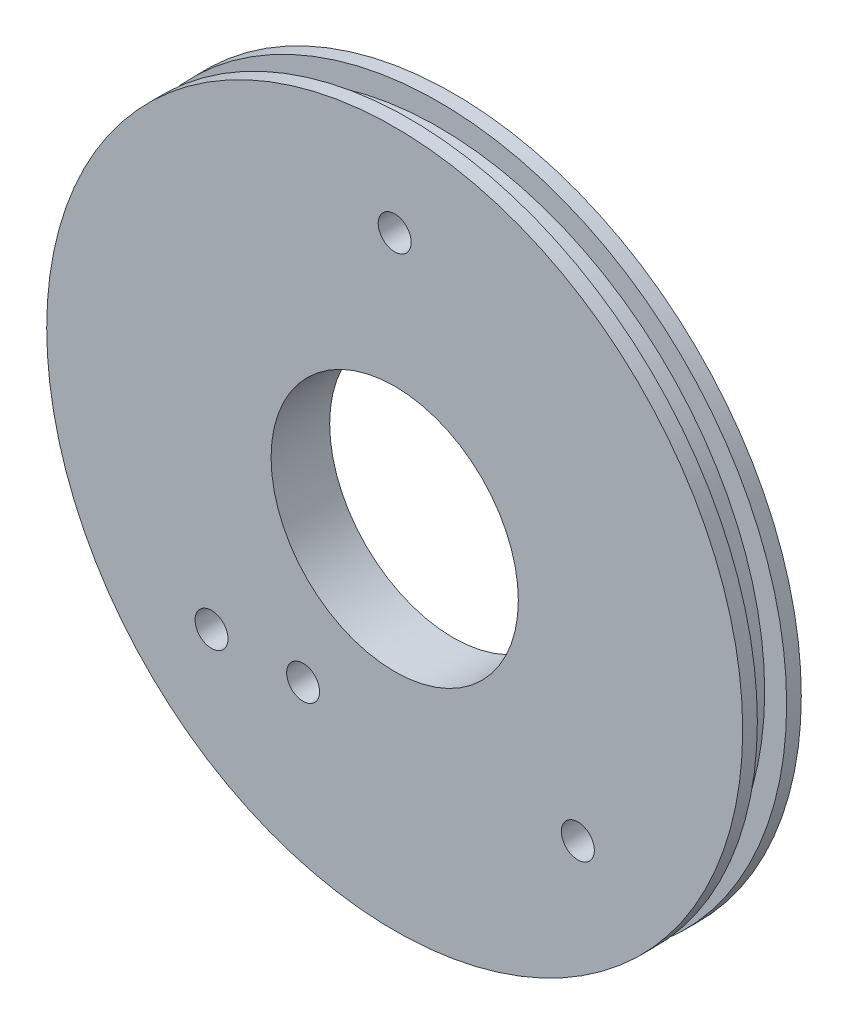
SolidWorks part; units mm, degrees
ref_plane "Front Plane" through (0, 0, 0) normal (0, 0, 1) x (1, 0, 0)
ref_plane "Top Plane" through (0, 0, 0) normal (0, 1, 0) x (1, 0, 0)
ref_plane "Right Plane" through (0, 0, 0) normal (1, 0, 0) x (0, 0, -1)
sketch "Sketch2" plane through (0, 0, 0) normal (0, 0, 1) x (1, 0, 0)
  circle A0 centre (0, 0) radius 89
  circle A1 centre (0, 0) radius 95
  dimension "180" = 178
  dimension "D2" = 190
extrude "Boss-Extrude1" add sketch "Sketch2" along normal blind 8 and the other way blind 8 contours A1 A0 | A0 region at (-92.313, 0, 0)
extrude "Cut-Extrude1" cut sketch "Sketch2<5>" against normal blind 4 and the other way blind 4
sketch "Sketch2<5>" plane through (0, 0, 0) normal (0, 0, 1) x (1, 0, 0) same geometry as "Sketch2"
sketch "Sketch3" plane through (0, 0, 8) normal (0, 0, 1) x (1, 0, 0)
  line L0 (0, 33.75) -> (0, -33.75) construction
  line L1 (41.5, 33.75) -> (-78.5, 33.75)
  line L2 (41.5, 33.75) -> (41.5, -33.75)
  line L3 (41.5, -33.75) -> (-78.5, -33.75) construction
  line L4 (-78.5, 33.75) -> (-78.5, -33.75) construction
  line L5 (31, 33.75) -> (31, -33.75) construction
  line L6 (41.5, 0) -> (-78.5, 0) construction
  line L7 (-78.5, 28.75) -> (-43.5, 28.75)
  line L8 (-43.5, 28.75) -> (-43.5, -33.75)
  line L9 (-78.5, 33.75) -> (-78.5, 28.75)
  line L10 (-43.5, -33.75) -> (41.5, -33.75)
  circle A0 centre (0, 0) radius 31
  circle A1 centre (0, 0) radius 33.75
  point P9 (0, 0)
  dimension "D3" = 62
  dimension "D7" = 67.5
  dimension "D1" = 10.5
  dimension "D2" = 120
  dimension "D4" = 67.5
  dimension "D5" = 5
  dimension "D6" = 35
sketch "Sketch4" plane through (0, 0, -8) normal (0, 0, 1) x (1, 0, 0)
  line L0 (0, 33.75) -> (0, -33.75) construction
  line L1 (41.5, 33.75) -> (-78.5, 33.75)
  line L2 (41.5, 33.75) -> (41.5, -33.75)
  line L3 (41.5, -33.75) -> (-78.5, -33.75) construction
  line L4 (-78.5, 33.75) -> (-78.5, -33.75) construction
  line L5 (31, 33.75) -> (31, -33.75) construction
  line L6 (41.5, 0) -> (-78.5, 0) construction
  line L7 (-78.5, 28.75) -> (-43.5, 28.75)
  line L8 (-43.5, 28.75) -> (-43.5, -33.75)
  line L9 (-78.5, 33.75) -> (-78.5, 28.75)
  line L10 (-43.5, -33.75) -> (41.5, -33.75)
  circle A0 centre (0, 0) radius 31
  point P9 (0, 0)
  dimension "D3" = 62
  dimension "D1" = 10.5
  dimension "D2" = 120
  dimension "D4" = 67.5
  dimension "D5" = 5
  dimension "D6" = 35
ref_plane "Plane1" through (0, -33.75, 0) normal (0, 1, 0) x (1, 0, 0)
sketch "Sketch7" plane through (0, 0, 8) normal (0, 0, 1) x (1, 0, 0)
  line L0 (0, -33.75) -> (0, -48.75) construction
  line L1 (-50, -48.75) -> (50, -48.75) construction
  line L2 (0, -48.75) -> (20, -48.75) construction
  line L3 (0, -48.75) -> (-6.4741, -48.75) construction
  circle A0 centre (-50, -48.75) radius 4.5
  circle A1 centre (50, -48.75) radius 4.5
  circle A5 centre (-25, -48.75) radius 4.5
  point P7 (0, -48.75)
  dimension "D3" = 9
  dimension "D4" = 9
  dimension "D5" = 9
  dimension "D1" = 100
  dimension "D2" = 15
  dimension "D6" = 25
extrude "Cut-Extrude2" cut sketch "Sketch7" against normal blind 167
extrude "Cut-Extrude3" cut sketch "Sketch3" against normal blind 43 contours L1 A1 L10 A0 | A0 | A1 region at (23.1899, 23.1899, 8) region at (0, 0, 8)
sketch "Sketch10" plane through (0, 0, -8) normal (0, 0, -1) x (-1, 0, 0)
  line L0 (0, 0) -> (0, 70) construction
  circle A0 centre (0, 70) radius 4.5
  circle A1 centre (0, 70) radius 6
  dimension "D2" = 9
  dimension "D3" = 12
  dimension "D1" = 70
extrude "Cut-Extrude4" cut sketch "Sketch10" against normal blind 60 and the other way blind 112 contours A0 region at (0, 70, -8)
